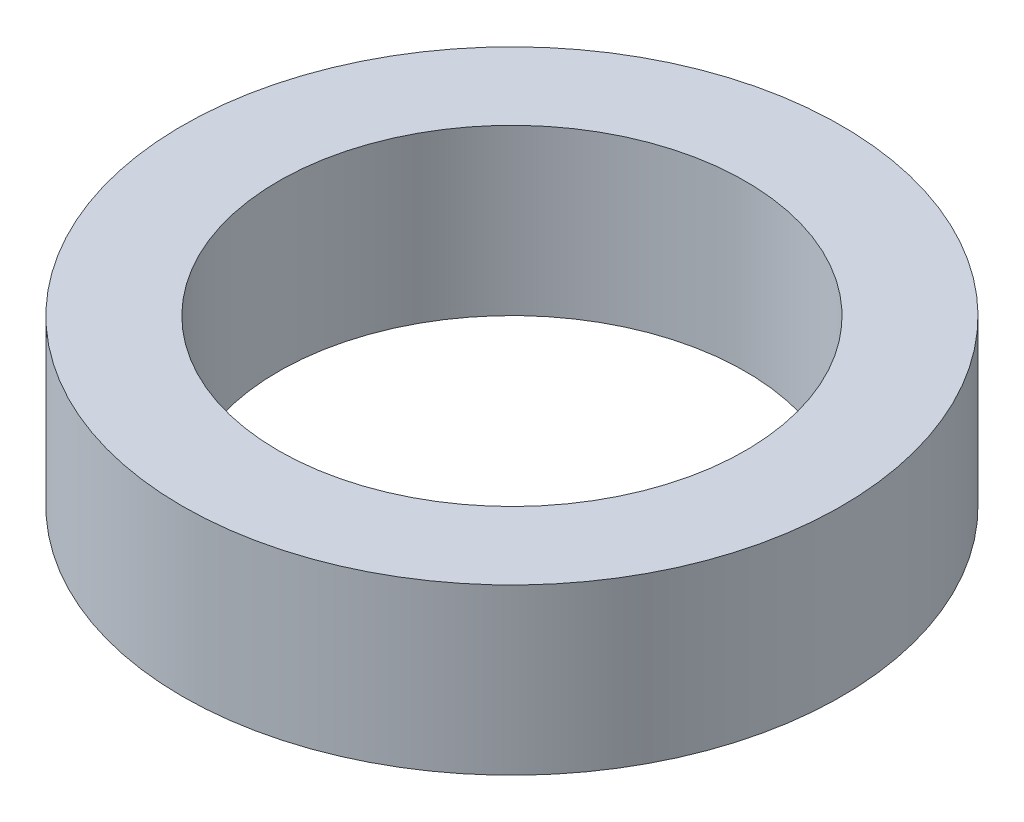
SolidWorks part; units mm, degrees
ref_plane "Front Plane" through (0, 0, 0) normal (0, 0, 1) x (1, 0, 0)
ref_plane "Top Plane" through (0, 0, 0) normal (0, 1, 0) x (1, 0, 0)
ref_plane "Right Plane" through (0, 0, 0) normal (1, 0, 0) x (0, 0, -1)
sketch "Sketch1" plane through (0, 0, 0) normal (0, 1, 0) x (1, 0, 0)
  circle A0 centre (0, 0) radius 60
  dimension "FLANGE_OD" = 120
extrude "Boss-Extrude1" add sketch "Sketch1" along normal blind 30
sketch "Sketch2" plane through (0, 0, 0) normal (0, 1, 0) x (1, 0, 0)
  circle A0 centre (0, 0) radius 42.5
  dimension "BORE_D" = 85
extrude "Cut-Extrude1" cut sketch "Sketch2" along normal through all
sketch "Sketch3" plane through (0, 30, 0) normal (0, 1, 0) x (1, 0, 0)
  circle A0 centre (0, 0) radius 23.6246 construction
  circle A1 centre (-23.6246, 0) radius 2.1984
  dimension "BOLT_D" = 4.3968
  dimension "BOLT_PCD" = 47.2492
extrude "Cut-Extrude2" cut sketch "Sketch3" against normal blind 24.2214 rebuild error yes
pattern_circular "CirPattern1" count 6 over 360 rebuild error yes
